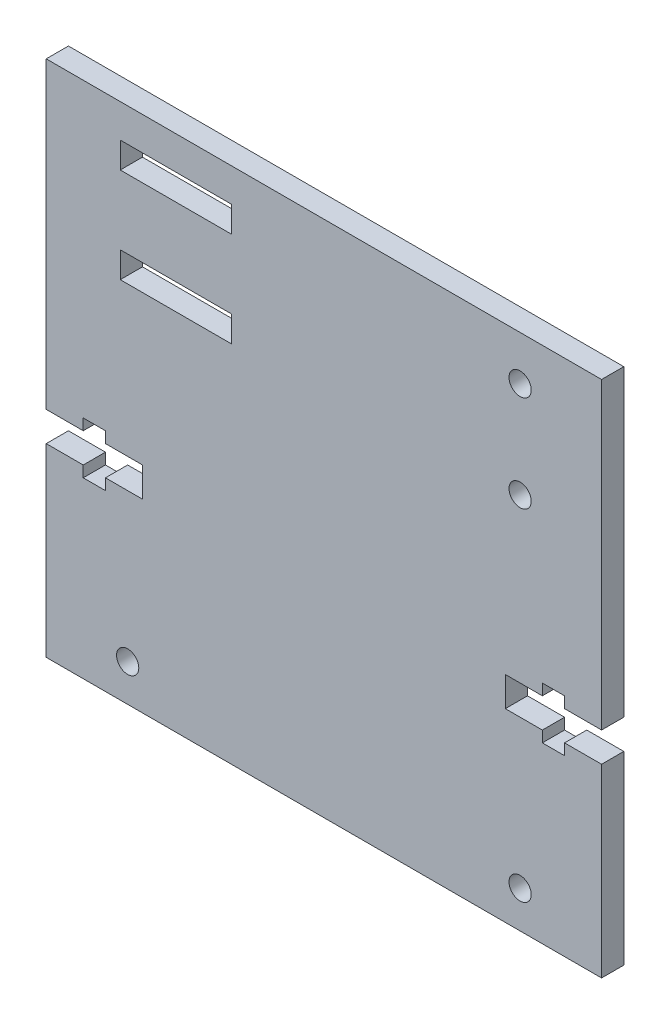
SolidWorks part; units mm, degrees
ref_plane "Plan de face" through (0, 0, 0) normal (0, 0, 1) x (1, 0, 0)
ref_plane "Plan de dessus" through (0, 0, 0) normal (0, 1, 0) x (1, 0, 0)
ref_plane "Plan de droite" through (0, 0, 0) normal (1, 0, 0) x (0, 0, -1)
sketch "Esquisse1" plane through (0, 0, 0) normal (0, 0, 1) x (1, 0, 0)
  line L0 (10, 65.5) -> (25, 65.5)
  line L1 (0, 0) -> (75, 0)
  line L2 (0, 0) -> (0, 70)
  line L3 (0, 70) -> (75, 70)
  line L4 (75, 0) -> (75, 70)
  line L5 (10, 52.6718) -> (25, 52.6718)
  line L6 (10, 52.6718) -> (10, 49.1718)
  line L7 (10, 49.1718) -> (25, 49.1718)
  line L8 (25, 52.6718) -> (25, 49.1718)
  line L9 (10, 65.5) -> (10, 62)
  line L10 (10, 62) -> (25, 62)
  line L11 (25, 65.5) -> (25, 62)
  line L12 (75, 25) -> (70, 25)
  line L13 (70, 25) -> (70, 23.5)
  line L14 (70, 23.5) -> (67, 23.5)
  line L15 (67, 23.5) -> (67, 25)
  line L16 (67, 25) -> (62, 25)
  line L17 (62, 25) -> (62, 29)
  line L18 (62, 29) -> (67, 29)
  line L19 (67, 29) -> (67, 30.5)
  line L20 (67, 30.5) -> (70, 30.5)
  line L21 (70, 30.5) -> (70, 29)
  line L22 (70, 29) -> (75, 29)
  line L23 (75, 29) -> (75, 25)
  line L24 (37.5, 0) -> (37.5, 93.5495) construction
  line L25 (0, 29) -> (0, 25)
  line L26 (5, 29) -> (0, 29)
  line L27 (5, 30.5) -> (5, 29)
  line L28 (8, 30.5) -> (5, 30.5)
  line L29 (8, 29) -> (8, 30.5)
  line L30 (13, 29) -> (8, 29)
  line L31 (13, 25) -> (13, 29)
  line L32 (8, 25) -> (13, 25)
  line L33 (8, 23.5) -> (8, 25)
  line L34 (5, 23.5) -> (8, 23.5)
  line L35 (5, 25) -> (5, 23.5)
  line L36 (0, 25) -> (5, 25)
  circle A0 centre (11, 5) radius 1.5
  circle A1 centre (64, 5) radius 1.5
  circle A2 centre (64, 51) radius 1.5
  circle A3 centre (64, 64) radius 1.5
  dimension "D3" = 3
  dimension "D1" = 70
  dimension "D2" = 75
  dimension "D4" = 5
  dimension "D5" = 11
  dimension "D6" = 25
  dimension "D7" = 11
  dimension "D8" = 5
  dimension "D9" = 3
  dimension "D10" = 6
  dimension "D11" = 19
  dimension "D12" = 15
  dimension "D13" = 3.5
  dimension "D14" = 4.5
  dimension "D15" = 10
  dimension "D16" = 1.5
  dimension "D17" = 4
  dimension "D18" = 37.5
extrude "Boss.-Extru.1" add sketch "Esquisse1" along normal blind 3 contours L1 L24 L3 L2 L26 L27 L28 L29 L30 L31 L32 L33 L34 L35 L36 L5 L8 L7 L6 L0 L11 L10 L9 A0 | L24 L1 L4 L12 L13 L14 L15 L16 L17 L18 L19 L20 L21 L22 L3 A3 A2 A1 region at (19.1306, 34.329, 0) region at (55.8915, 35.1502, 0)
